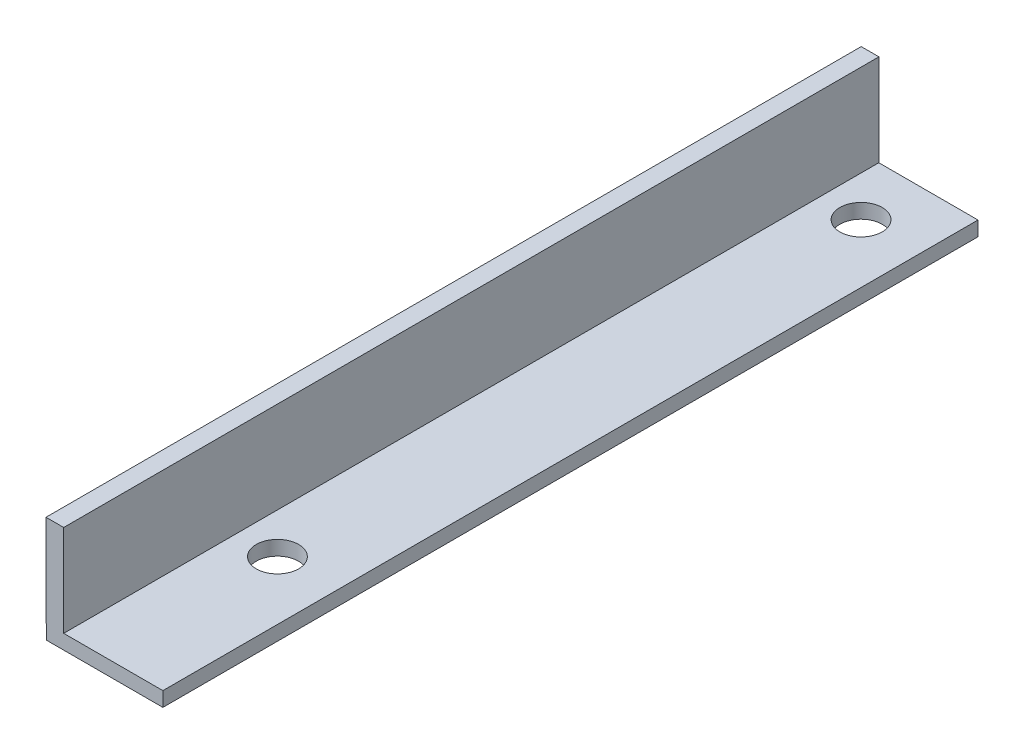
SolidWorks part; units mm, degrees
ref_plane "Front Plane" through (0, 0, 0) normal (0, 0, 1) x (1, 0, 0)
ref_plane "Top Plane" through (0, 0, 0) normal (0, 1, 0) x (1, 0, 0)
ref_plane "Right Plane" through (0, 0, 0) normal (1, 0, 0) x (0, 0, -1)
sketch "Sketch1" plane through (0, 0, 0) normal (0, 1, 0) x (1, 0, 0)
  line L1 (0, 101.5375) -> (12.7, 101.5375)
  line L2 (0, 101.5375) -> (0, 12.6375)
  line L3 (0, 12.6375) -> (12.7, 12.6375)
  line L4 (12.7, 101.5375) -> (12.7, 12.6375)
  circle A0 centre (6.2932, 95.1875) radius 2.31
  circle A5 centre (6.2932, 31.5375) radius 2.31
  dimension "D1" = 12.7
  dimension "D2" = 88.9
extrude "Boss-Extrude1" add sketch "Sketch1" along normal blind 1.5875
sketch "Sketch3" plane through (0, 1.5875, 0) normal (0, 1, 0) x (1, 0, 0)
  line L0 (0, 12.6375) -> (12.7, 12.6375) construction
  line L1 (1.8825, 101.5477) -> (-0.0473, 101.5477)
  line L2 (1.8825, 101.5477) -> (1.8825, 12.6375)
  line L3 (1.8825, 12.6375) -> (-0.0473, 12.6375)
  line L4 (-0.0473, 101.5477) -> (-0.0473, 12.6375)
extrude "Boss-Extrude3" add sketch "Sketch3" along normal blind 10
